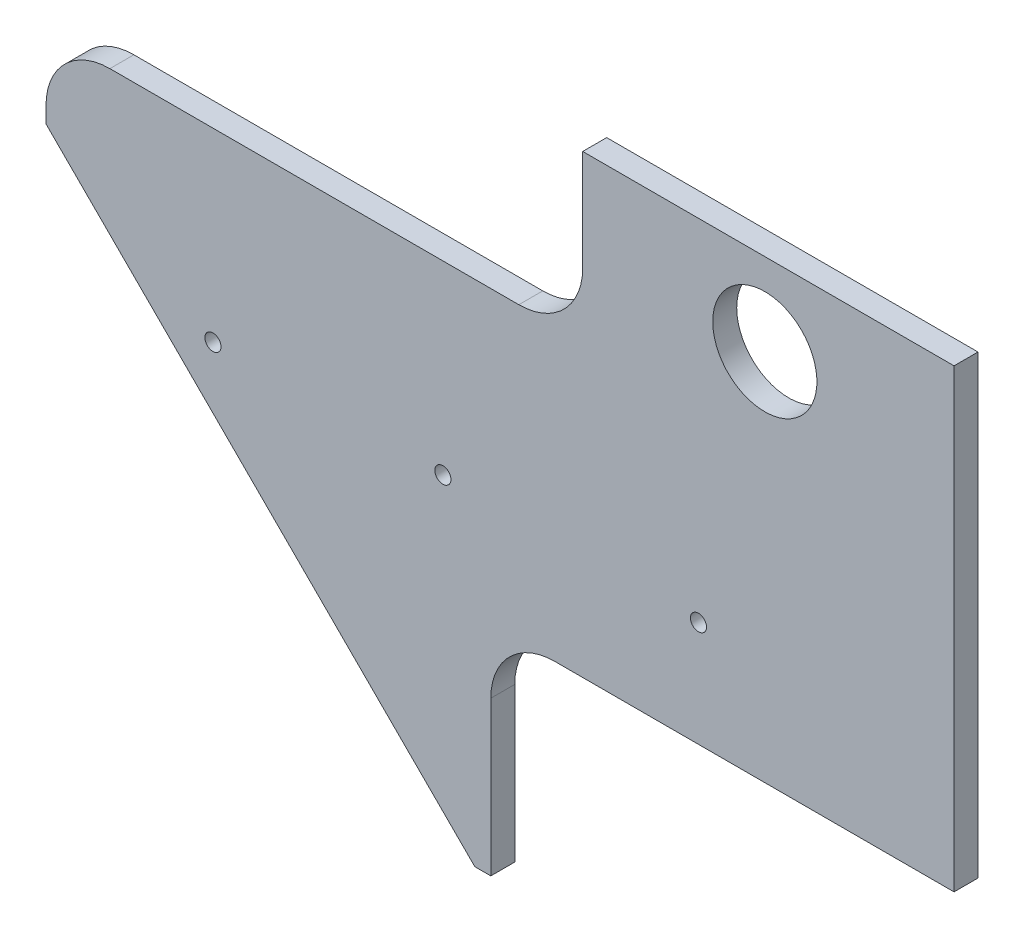
SolidWorks part; units mm, degrees
ref_plane "Front Plane" through (0, 0, 0) normal (0, 0, 1) x (1, 0, 0)
ref_plane "Top Plane" through (0, 0, 0) normal (0, 1, 0) x (1, 0, 0)
ref_plane "Right Plane" through (0, 0, 0) normal (1, 0, 0) x (0, 0, -1)
sketch "Sketch1" plane through (0, 0, 0) normal (0, 0, 1) x (1, 0, 0)
  line L0 (-138.2594, 48.9915) -> (32.2106, -121.4785)
  line L1 (32.2106, -121.4785) -> (222.7106, -121.4785)
  line L2 (-138.2594, 146.2068) -> (-138.2594, 48.9915)
  line L3 (-138.2594, 146.2068) -> (222.7106, 146.2068)
  line L4 (222.7106, -121.4785) -> (222.7106, 146.2068)
  circle A0 centre (147.4906, 113.4715) radius 20.701
  circle A2 centre (147.4906, 113.4715) radius 69.85 construction
  circle A3 centre (147.4906, 113.4715) radius 285.75 construction
  point P0 (0, 0)
  point P2 (147.4906, 113.4715)
  dimension "D4" = 234.95
  dimension "D1" = 45
  dimension "D2" = 267.6854
  dimension "D5" = 247.65
extrude "Boss-Extrude1" add sketch "Sketch1" along normal blind 9.525
sketch "Sketch2" plane through (0, 0, 9.525) normal (0, 0, 1) x (1, 0, 0)
  line L0 (32.2106, -121.4785) -> (222.7106, -121.4785) construction
  line L1 (222.7106, -121.4785) -> (38.5606, -121.4785)
  line L2 (222.7106, -121.4785) -> (222.7106, -34.9082)
  line L3 (222.7106, -34.9082) -> (38.5606, -34.9082)
  line L4 (38.5606, -121.4785) -> (38.5606, -34.9082)
extrude "Cut-Extrude1" cut sketch "Sketch2" against normal through all contours L3 L4 L1 L2
fillet "Fillet1" radius 25.4 1 edges at (38.5606, -34.9082, 4.7625)
sketch "Sketch4" plane through (0, 0, 9.525) normal (0, 0, 1) x (1, 0, 0)
  line L1 (-138.2594, 146.2068) -> (-138.2594, 48.9915) construction
  line L3 (-138.2594, 146.2068) -> (75.1006, 146.2068)
  line L4 (-138.2594, 146.2068) -> (-138.2594, 80.7415)
  line L5 (-138.2594, 80.7415) -> (75.1006, 80.7415)
  line L6 (75.1006, 146.2068) -> (75.1006, 80.7415)
extrude "Cut-Extrude2" cut sketch "Sketch4" against normal through all contours L5 L6 L3 L4
fillet "Fillet2" radius 25.4 2 edges at (-138.2594, 80.7415, 4.7625) (75.1006, 80.7415, 4.7625)
hole_wizard "Ø6.4 (6.4) Diameter Hole2" positions "Sketch15" profile "Sketch14" hole size "Ø6.4" standard "Lanco STD" end condition through all
sketch "Sketch15" plane through (0, 0, 0) normal (0, 0, -1) x (-1, 0, 0)
  point P3 (-121.1106, 7.0429)
  point P6 (-19.5106, 7.0429)
  point P9 (71.8957, 7.0429)
sketch "Sketch14" plane through (121.1106, 7.0429, 0) normal (1, 0, 0) x (0, 1, 0)
  line L0 (0, 0) -> (0, 9.525)
  line L1 (0, 9.525) -> (3.2, 9.525)
  line L2 (3.2, 9.525) -> (3.2, 0)
  line L5 (3.2, 0) -> (0, 0)
  line L11 (0, -6.35) -> (0, 107.95) construction
  dimension "Thru Hole Dia." = 6.4
  dimension "Thru Hole Depth" = 9.525
